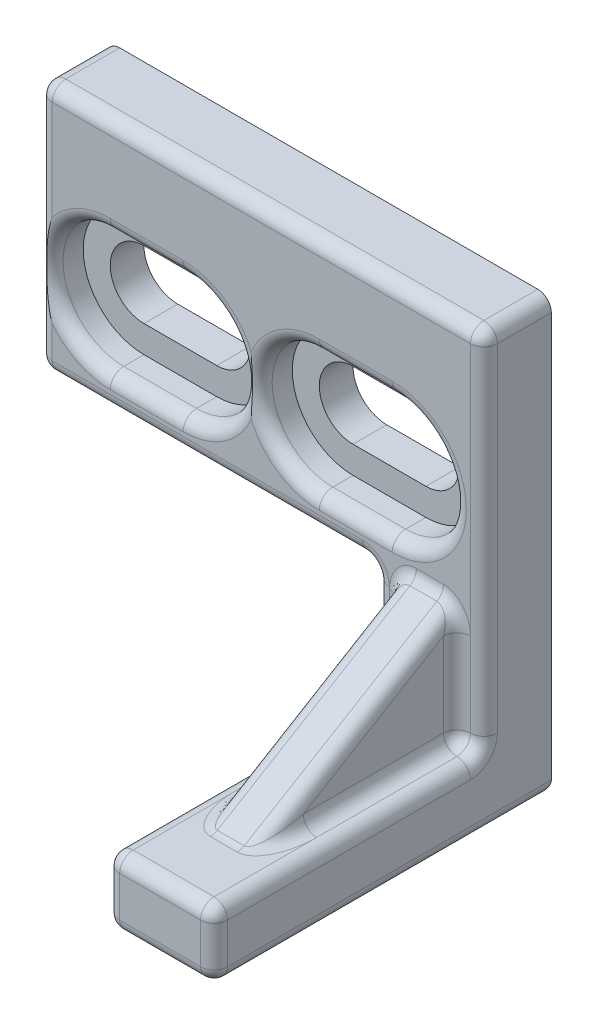
SolidWorks part; units mm, degrees
ref_plane "Front Plane" through (0, 0, 0) normal (0, 0, 1) x (1, 0, 0)
ref_plane "Top Plane" through (0, 0, 0) normal (0, 1, 0) x (1, 0, 0)
ref_plane "Right Plane" through (0, 0, 0) normal (1, 0, 0) x (0, 0, -1)
sketch "Sketch1" plane through (0, 0, 0) normal (0, 0, 1) x (1, 0, 0)
  line L0 (5.3, 6.8) -> (10.7, 6.8) construction
  line L1 (1, 0) -> (24, 0)
  line L2 (0, 1) -> (0, 17.6)
  line L3 (1, 18.6) -> (32, 18.6)
  line L4 (33, 12.648) -> (33, 17.6)
  line L5 (0, 0) -> (33, 18.6) construction
  line L6 (0, 18.6) -> (33, 12.648) construction
  line L9 (5.3, 9.3) -> (10.7, 9.3)
  line L12 (25, -1) -> (25, -13.4)
  line L13 (25, -13.4) -> (33, -13.4)
  line L14 (33, -13.4) -> (33, 12.648)
  line L15 (5.3, 4.3) -> (10.7, 4.3)
  line L16 (20.8, 6.8) -> (26.2, 6.8) construction
  line L17 (20.8, 9.3) -> (26.2, 9.3)
  line L18 (20.8, 4.3) -> (26.2, 4.3)
  arc A0 (0, 1) -> (1, 0) centre (1, 1) ccw
  arc A2 (33, 17.6) -> (32, 18.6) centre (32, 17.6) ccw
  arc A3 (1, 18.6) -> (0, 17.6) centre (1, 17.6) ccw
  arc A14 (25, -1) -> (24, 0) centre (24, -1) ccw
  arc A15 (5.3, 9.3) -> (5.3, 4.3) centre (5.3, 6.8) ccw
  arc A16 (10.7, 4.3) -> (10.7, 9.3) centre (10.7, 6.8) ccw
  arc A17 (20.8, 9.3) -> (20.8, 4.3) centre (20.8, 6.8) ccw
  arc A18 (26.2, 4.3) -> (26.2, 9.3) centre (26.2, 6.8) ccw
  point P4 (25, 14.0909)
  point P20 (8, 6.8)
  point P30 (23.5, 6.8)
  dimension "D3" = 1
  dimension "D4" = 4.3
  dimension "D5" = 4.3
  dimension "D6" = 5.3
  dimension "D7" = 25
  dimension "D8" = 1
  dimension "D9" = 33
  dimension "D15" = 5.4
  dimension "D12" = 5.4
  dimension "D1" = 18.6
  dimension "D2" = 8
  dimension "D10" = 5
  dimension "D11" = 5
  dimension "D13" = 26.2
  dimension "D14" = 32
extrude "Boss-Extrude1" add sketch "Sketch1" along normal blind 5
sketch "Sketch2" plane through (0, 0, 5) normal (0, 0, 1) x (1, 0, 0)
  line L0 (33, -13.4) -> (33, 17.6) construction
  line L1 (25, -13.4) -> (33, -13.4)
  line L2 (25, -13.4) -> (25, -8.4)
  line L3 (25, -8.4) -> (33, -8.4)
  line L4 (33, -13.4) -> (33, -8.4)
  line L5 (25, -13.4) -> (33, -8.4) construction
  line L6 (25, -8.4) -> (33, -13.4) construction
  point P4 (29, -10.9)
  dimension "D1" = 5
extrude "Boss-Extrude2" add sketch "Sketch2" along normal blind 20
sketch "Sketch3" plane through (0, 0, 5) normal (0, 0, 1) x (1, 0, 0)
  line L10 (10.7, 11.3) -> (5.3, 11.3)
  line L11 (5.3, 2.3) -> (10.7, 2.3)
  line L12 (10.7, 11.3) -> (5.3, 11.3)
  line L13 (5.3, 2.3) -> (10.7, 2.3)
  line L18 (26.2, 11.3) -> (20.8, 11.3)
  line L19 (20.8, 2.3) -> (26.2, 2.3)
  line L20 (26.2, 11.3) -> (20.8, 11.3)
  line L21 (20.8, 2.3) -> (26.2, 2.3)
  arc A13 (10.7, 2.3) -> (10.7, 11.3) centre (10.7, 6.8) ccw
  arc A14 (5.3, 11.3) -> (5.3, 2.3) centre (5.3, 6.8) ccw
  arc A15 (10.7, 2.3) -> (10.7, 11.3) centre (10.7, 6.8) ccw
  arc A16 (5.3, 11.3) -> (5.3, 2.3) centre (5.3, 6.8) ccw
  arc A23 (26.2, 2.3) -> (26.2, 11.3) centre (26.2, 6.8) ccw
  arc A24 (20.8, 11.3) -> (20.8, 2.3) centre (20.8, 6.8) ccw
  arc A25 (26.2, 2.3) -> (26.2, 11.3) centre (26.2, 6.8) ccw
  arc A26 (20.8, 11.3) -> (20.8, 2.3) centre (20.8, 6.8) ccw
  dimension "D3" = 9
  dimension "D1" = 2
  dimension "D2" = 2
extrude "Cut-Extrude1" cut sketch "Sketch3" against normal blind 2.5
sketch "Sketch4" plane through (33, 0, 0) normal (1, 0, 0) x (0, 0, -1)
  line L0 (-5, 0.6) -> (-20, -8.4)
  line L1 (-5, -8.4) -> (-5, 17.6) construction
  line L2 (-25, -8.4) -> (-5, -8.4) construction
  line L3 (-20, -8.4) -> (-5, -8.4)
  line L4 (-5, -8.4) -> (-5, 0.6)
  dimension "D1" = 15
  dimension "D2" = 9
extrude "Boss-Extrude3" add sketch "Sketch4" against normal blind 4 from offset 2 offset against normal yes
fillet "Fillet1" radius 1 34 edges at (0, 9.3, 5) (0.2929, 18.3071, 5) (16.5, 18.6, 5) (32.7071, 18.3071, 5) (33, 4.6, 5) (12.5, 0, 5) (0.2929, 0.2929, 5) (25, -4.7, 5) (24.7071, -0.2929, 5) (25, -8.4, 15) (33, -8.4, 15) (29, -8.4, 25) (33, -10.9, 25) (25, -10.9, 25) (25, -13.4, 12.5) (29, -13.4, 25) (33, -13.4, 12.5) (29, -13.4, 0) (8, 11.3, 5) (0.8, 6.8, 5) (8, 2.3, 5) (15.2, 6.8, 5) (23.5, 11.3, 5) (16.3, 6.8, 5) (23.5, 2.3, 5) (30.7, 6.8, 5) (31, -3.9, 5) (29, 0.6, 5) (27, -3.9, 5) (31, -3.9, 12.5) (27, -3.9, 12.5) (27, -8.4, 12.5) (29, -8.4, 20) (31, -8.4, 12.5)
